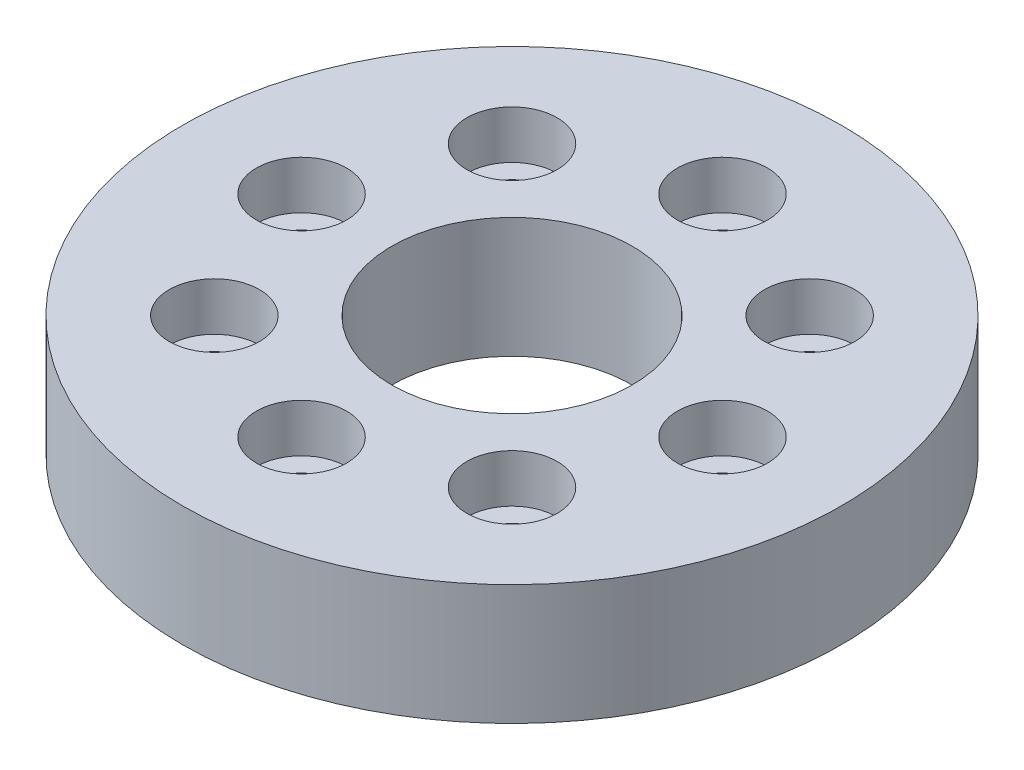
SolidWorks part; units mm, degrees
ref_plane "Front Plane" through (0, 0, 0) normal (0, 0, 1) x (1, 0, 0)
ref_plane "Top Plane" through (0, 0, 0) normal (0, 1, 0) x (1, 0, 0)
ref_plane "Right Plane" through (0, 0, 0) normal (1, 0, 0) x (0, 0, -1)
sketch "Sketch1" plane through (0, 0, 0) normal (0, 1, 0) x (1, 0, 0)
  line L0 (0, 10) -> (0, 25) construction
  circle A0 centre (0, 0) radius 10
  circle A1 centre (0, 0) radius 27.4
  circle A2 centre (0, 0) radius 25
  circle A3 centre (0, 17.5) radius 2
  circle A4 centre (12.3744, 12.3744) radius 2
  circle A5 centre (17.5, 0) radius 2
  circle A6 centre (12.3744, -12.3744) radius 2
  circle A7 centre (0, -17.5) radius 2
  circle A8 centre (-12.3744, -12.3744) radius 2
  circle A9 centre (-17.5, 0) radius 2
  circle A10 centre (-12.3744, 12.3744) radius 2
  point P26 (0, 0)
  dimension "D1" = 20
  dimension "D2" = 54.8
  dimension "D3" = 50
  dimension "D4" = 4
  dimension "D5" = 8
extrude "Boss-Extrude1" add sketch "Sketch1" along normal blind 10 contours A1 A2 | A0 A3 A2 A10 A9 A8 A7 A6 A5 A4 region at (-26.625, 0, 0) region at (-24.2929, 0, 0)
sketch "Sketch2" plane through (0, 10, 0) normal (0, 1, 0) x (1, 0, 0)
  circle A0 centre (-12.3744, 12.3744) radius 3.75
  circle A1 centre (0, 17.5) radius 3.75
  circle A2 centre (12.3744, 12.3744) radius 3.75
  circle A3 centre (17.5, 0) radius 3.75
  circle A4 centre (12.3744, -12.3744) radius 3.75
  circle A5 centre (0, -17.5) radius 3.75
  circle A6 centre (-12.3744, -12.3744) radius 3.75
  circle A7 centre (-17.5, 0) radius 3.75
  point P20 (0, 0)
  dimension "D1" = 7.5
  dimension "D2" = 8
extrude "Cut-Extrude1" cut sketch "Sketch2" against normal blind 4
